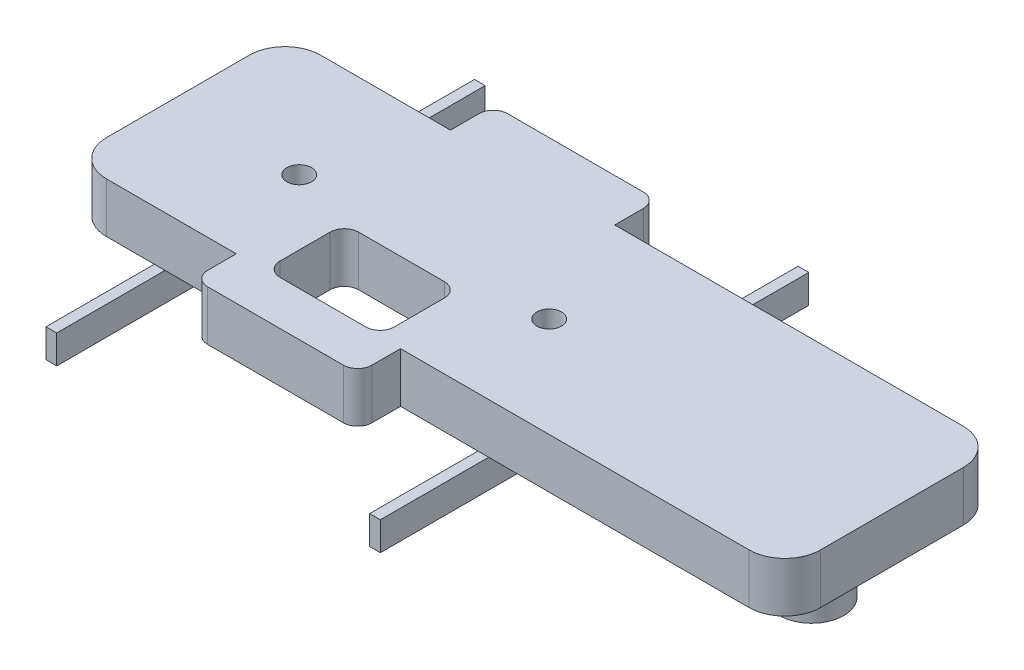
SolidWorks part; units mm, degrees
ref_plane "Front Plane" through (0, 0, 0) normal (0, 0, 1) x (1, 0, 0)
ref_plane "Top Plane" through (0, 0, 0) normal (0, 1, 0) x (1, 0, 0)
ref_plane "Right Plane" through (0, 0, 0) normal (1, 0, 0) x (0, 0, -1)
sketch "Sketch1" plane through (0, 0, 0) normal (0, 1, 0) x (1, 0, 0)
  line L1 (-45.1945, 17.8802) -> (54.8055, 17.8802)
  line L2 (-45.1945, 17.8802) -> (-45.1945, -12.1198)
  line L3 (-45.1945, -12.1198) -> (54.8055, -12.1198)
  line L4 (54.8055, 17.8802) -> (54.8055, -12.1198)
  point P4 (-35.8894, -11.2356)
  dimension "D1" = 100
  dimension "D2" = 30
extrude "Boss-Extrude1" add sketch "Sketch1" along normal blind 7
ref_plane "Plane1" through (0, -1, 0) normal (0, -1, 0) x (-1, 0, 0)
sketch "Sketch2" plane through (0, -1, 0) normal (0, -1, 0) x (-1, 0, 0)
  line L0 (-54.8055, 2.8802) -> (57.5711, 2.8802) construction
  line L1 (-41.1646, -0.0198) -> (-44.5646, -0.0198)
  line L2 (-41.1646, -0.0198) -> (-41.1646, 5.7802)
  line L3 (-41.1646, 5.7802) -> (-44.5646, 5.7802)
  line L4 (-44.5646, -0.0198) -> (-44.5646, 5.7802)
  line L5 (-54.8055, -12.1198) -> (-54.8055, 17.8802) construction
  line L6 (-42.8646, -12.1198) -> (-42.8646, 27.765) construction
  line L8 (45.1945, -12.1198) -> (-54.8055, -12.1198) construction
  dimension "D1" = 3.4
  dimension "D2" = 5.8
  dimension "D3" = 1.7
  dimension "D4" = 2.9
extrude "Boss-Extrude2" add sketch "Sketch2" along normal blind 6 separate body
shell "Shell1" thickness 1 removed face at (42.8646, -7, -2.8802) outward yes
sketch "Sketch3" plane through (0, 0, 0) normal (0, -1, 0) x (-1, 0, 0)
  line L0 (-42.8646, -0.0198) -> (-42.8646, 11.0227) construction
  line L1 (-44.5646, -0.0198) -> (-41.1646, -0.0198) construction
  line L2 (-41.1646, 2.8802) -> (-49.8164, 2.8802) construction
  line L3 (-41.1646, -0.0198) -> (-41.1646, 5.7802) construction
  point P9 (-42.8646, 2.8802)
sketch "Sketch4" plane through (0, 0, 0) normal (0, -1, 0) x (-1, 0, 0)
  circle A0 centre (-42.9099, 3.5376) radius 4.5
  circle A1 centre (-42.9099, 3.5376) radius 3.7
extrude "Boss-Extrude3" add sketch "Sketch4" along normal blind 10
sketch "Sketch5" plane through (0, 0, 0) normal (0, -1, 0) x (-1, 0, 0)
  circle A0 centre (-42.8646, 2.8802) radius 4.25
  circle A1 centre (-42.8646, 2.8802) radius 5.5
extrude "Boss-Extrude4" add sketch "Sketch5" along normal blind 4
fillet "Fillet1" radius 5 4 edges at (-45.1945, 3.5, -17.8802) (-45.1945, 3.5, 12.1198) (54.8055, 3.5, -17.8802) (54.8055, 3.5, 12.1198)
sketch "Sketch6" plane through (0, 0, 0) normal (0, -1, 0) x (-1, 0, 0)
  line L0 (40.1945, -12.1198) -> (-49.8055, -12.1198) construction
  line L1 (22.0125, -12.1198) -> (-0.9875, -12.1198)
  line L2 (22.0125, -12.1198) -> (22.0125, -18.1198)
  line L3 (22.0125, -18.1198) -> (-0.9875, -18.1198)
  line L4 (-0.9875, -12.1198) -> (-0.9875, -18.1198)
  line L5 (45.1945, 2.8802) -> (44.2396, 2.8802) construction
  line L6 (45.1945, 12.8802) -> (45.1945, -7.1198) construction
  line L7 (22.0125, 23.8802) -> (-0.9875, 23.8802)
  line L8 (-0.9875, 17.8802) -> (-0.9875, 23.8802)
  line L9 (22.0125, 17.8802) -> (-0.9875, 17.8802)
  line L10 (22.0125, 17.8802) -> (22.0125, 23.8802)
  dimension "D1" = 6
  dimension "D2" = 23
extrude "Boss-Extrude5" add sketch "Sketch6" against normal up to surface (7 mm away) up to face at (4.8055, 7, -2.8802)
sketch "Sketch7" plane through (0, 0, 0) normal (0, -1, 0) x (-1, 0, 0)
  line L0 (40.1945, -12.1198) -> (22.0125, -12.1198) construction
  line L1 (-0.9875, -12.1198) -> (-49.8055, -12.1198) construction
  circle A0 centre (27.1973, 1.8802) radius 1.725
  circle A1 centre (-7.8027, 1.8802) radius 1.725
  dimension "D1" = 35
  dimension "D2" = 14
  dimension "D3" = 14
extrude "Cut-Extrude1" cut sketch "Sketch7" against normal up to surface (7 mm away) up to face at (-2.8535, 7, -2.8802)
fillet "Fillet2" radius 2 4 edges at (0.9875, 3.5, -23.8802) (-22.0125, 3.5, -23.8802) (0.9875, 3.5, 18.1198) (-22.0125, 3.5, 18.1198)
sketch "Sketch8" plane through (0, 0, 0) normal (0, -1, 0) x (-1, 0, 0)
  line L0 (1.0125, -18.1198) -> (20.0125, -18.1198) construction
  line L1 (18.0789, -11.9198) -> (2.0789, -11.9198)
  line L2 (18.0789, -11.9198) -> (18.0789, -0.9198)
  line L3 (18.0789, -0.9198) -> (2.0789, -0.9198)
  line L4 (2.0789, -11.9198) -> (2.0789, -0.9198)
  dimension "D1" = 16
  dimension "D2" = 11
  dimension "D3" = 6.2
extrude "Cut-Extrude2" cut sketch "Sketch8" against normal up to surface (7 mm away) up to face at (-27.1973, 7, -0.1552)
fillet "Fillet3" radius 2 4 edges at (-2.0789, 3.5, 0.9198) (-18.0789, 3.5, 0.9198) (-2.0789, 3.5, 11.9198) (-18.0789, 3.5, 11.9198)
sketch "Sketch9" plane through (0, 0, 0) normal (0, -1, 0) x (-1, 0, 0)
  line L0 (33.4881, 32.7056) -> (33.4881, -27.2944)
  line L1 (31.9881, 32.7056) -> (31.9881, -27.2944)
  line L2 (33.4881, -27.2944) -> (31.9881, -27.2944)
  line L3 (33.4881, 32.7056) -> (31.9881, 32.7056)
  line L4 (16.0789, -0.9198) -> (4.0789, -0.9198) construction
  line L5 (10.0789, -0.9198) -> (10.0789, -27.2944) construction
  line L6 (-13.3304, 32.7056) -> (-13.3304, -27.2944)
  line L7 (-13.3304, -27.2944) -> (-11.8304, -27.2944)
  line L8 (-11.8304, 32.7056) -> (-11.8304, -27.2944)
  line L9 (-13.3304, 32.7056) -> (-11.8304, 32.7056)
  dimension "D1" = 60
  dimension "D2" = 1.5
extrude "Boss-Extrude6" add sketch "Sketch9" along normal blind 4
